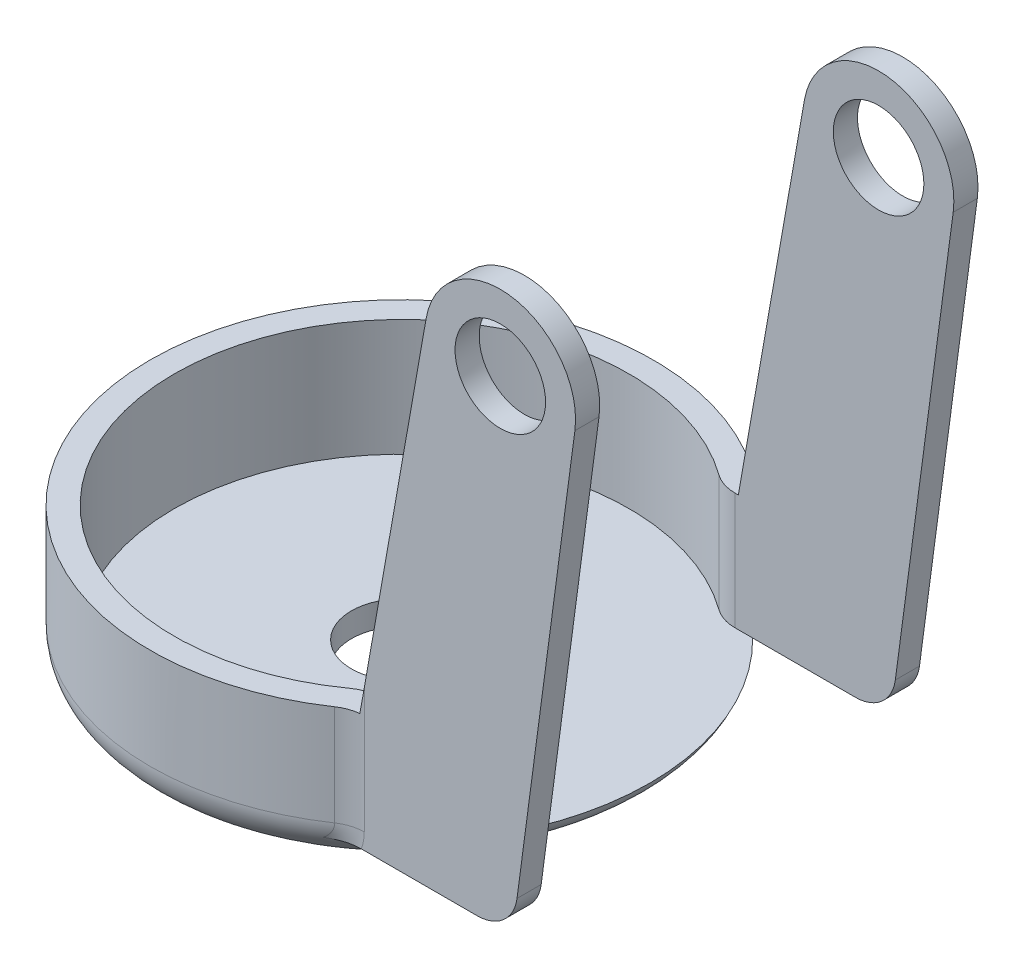
SolidWorks part; units mm, degrees
ref_plane "Ebene vorne" through (0, 0, 0) normal (0, 0, 1) x (1, 0, 0)
ref_plane "Ebene oben" through (0, 0, 0) normal (0, 1, 0) x (1, 0, 0)
ref_plane "Ebene rechts" through (0, 0, 0) normal (1, 0, 0) x (0, 0, -1)
sketch "Skizze1" plane through (0, 0, 0) normal (0, 1, 0) x (1, 0, 0)
  circle A0 centre (0, 0) radius 12.5
  dimension "D1" = 25
extrude "Aufsatz-Linear austragen1" add sketch "Skizze1" along normal blind 1.2
sketch "Skizze2" plane through (0, 1.2, 0) normal (0, 1, 0) x (1, 0, 0)
  line L0 (7.5, 10) -> (15.5, 10)
  line L1 (7.5, -10) -> (15.5, -10)
  line L2 (-1.0558, 0) -> (22.5402, 0) construction
  line L3 (7.0887, 8.8) -> (15.5, 8.8)
  line L4 (8.6648, -8.8) -> (15.5, -8.8)
  line L5 (15.5, 10) -> (15.5, 8.8)
  line L6 (15.5, -8.8) -> (15.5, -10)
  line L7 (8.6648, -8.8) -> (7.0887, -8.8)
  arc A0 (7.5, 10) -> (7.5, -10) centre (0, 0) ccw
  arc A1 (7.0887, 8.8) -> (7.0887, -8.8) centre (0, 0) ccw
  dimension "D1" = 25
  dimension "D2" = 22.6
  dimension "D5" = 15.5
  dimension "D3" = 20
  dimension "D4" = 17.6
extrude "Aufsatz-Linear austragen2" add sketch "Skizze2" along normal blind 30
sketch "Skizze4" plane through (0, 0, 10) normal (0, 0, 1) x (1, 0, 0)
  line L0 (15.5, 1.2) -> (19.5, 31.2)
  line L1 (19.5, 31.2) -> (15.5, 31.2)
  line L2 (15.5, 31.2) -> (15.5, 1.2)
  line L3 (-12.5, 31.2) -> (-12.5, 0) construction
  dimension "D1" = 32
extrude "Aufsatz-Linear austragen3" add sketch "Skizze4" against normal up to surface (1.2 mm away) up to face at (10.811, 13.2, 8.8)
sketch "Skizze5" plane through (0, 0, -10) normal (0, 0, -1) x (-1, 0, 0)
  line L0 (-15.5, 1.2) -> (-19.5, 31.2)
  line L1 (-19.5, 31.2) -> (-15.5, 31.2)
  line L2 (-15.5, 31.2) -> (-15.5, 1.2)
extrude "Aufsatz-Linear austragen4" add sketch "Skizze5" against normal up to surface (1.2 mm away) up to face at (10.811, 13.2, -8.8)
sketch "Skizze3" plane through (0, 0, 0) normal (0, 0, 1) x (1, 0, 0)
  line L0 (-12.5, 7) -> (7.9282, 7)
  line L1 (-12.5, 31.2) -> (-12.5, 0) construction
  line L2 (7.9282, 7) -> (11.2166, 25.6495)
  line L4 (19.5, 31.2) -> (-12.5, 31.2)
  line L5 (-12.5, 31.2) -> (-12.5, 7)
  line L8 (-12.5, 0) -> (12.5, 0) construction
  line L9 (15.5, 1.2) -> (19.5, 31.2) construction
  line L10 (19.5, 31.2) -> (18.6074, 24.5057)
  circle A0 centre (14.9, 25) radius 2.25
  arc A1 (18.6074, 24.5057) -> (11.2166, 25.6495) centre (14.9, 25) ccw
  dimension "D3" = 4.5
  dimension "D1" = 7
  dimension "D2" = 100
  dimension "D4" = 25
  dimension "D5" = 14.9
extrude "Schnitt-Linear austragen1" cut sketch "Skizze3" against normal mid plane 30
fillet "Verrundung2" radius 2 1 edges at (0, 0, 12.5)
fillet "Verrundung3" radius 2 6 edges at (7.4323, 1.5997, -10) (7.4169, 1.557, 10) (7.0887, 4.1, 8.8) (7.0887, 4.1, -8.8) (7.5, 4.5, -10) (7.5, 4.5, 10)
fillet "Fillet2" radius 2 1 edges at (15.5, 1.2, 9.4)
fillet "Fillet3" radius 2 1 edges at (15.5, 1.2, -9.4)
sketch "Skizze7" plane through (0, 0, 0) normal (0, -1, 0) x (1, 0, 0)
  circle A0 centre (0, 0) radius 2.5
  dimension "D1" = 5
extrude "Schnitt-Linear austragen2" cut sketch "Skizze7" against normal through all
